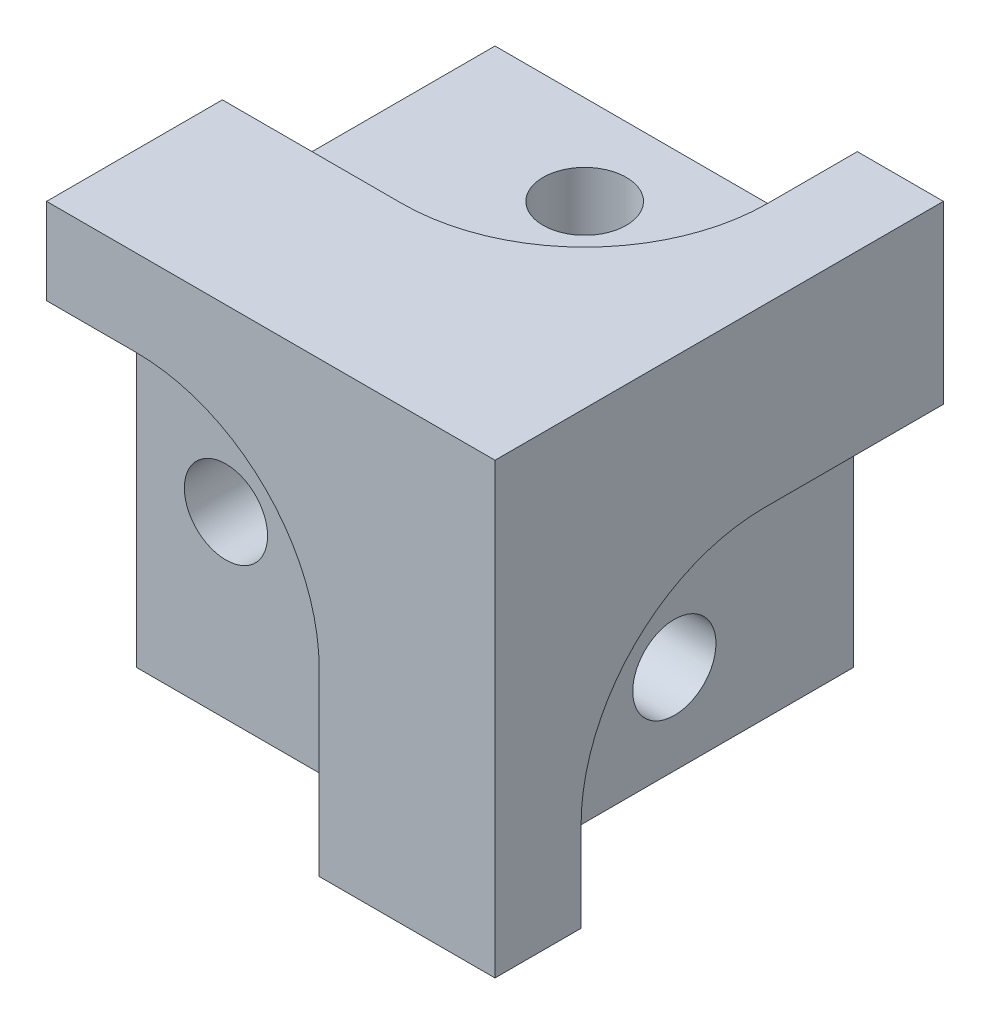
SolidWorks part; units mm, degrees
material "6061-T6 (SS)"
ref_plane "Front Plane" through (0, 0, 0) normal (0, 0, 1) x (1, 0, 0)
ref_plane "Top Plane" through (0, 0, 0) normal (0, 1, 0) x (1, 0, 0)
ref_plane "Right Plane" through (0, 0, 0) normal (1, 0, 0) x (0, 0, -1)
ref_axis "Axis1" [suppressed] through (0, 6.6, 0) along (0, -1, 0)
ref_axis "Axis2" [suppressed] through (0, 0, -6.6) along (0, 0, 1)
ref_plane "MIR-PLANE-1" through (0, 0, 0) normal (0, 0.7071, -0.7071) x (-1, 0, 0)
ref_plane "MIR-PLANE-2" through (0, 0, 0) normal (-0.7071, 0, 0.7071) x (0.7071, 0, 0.7071)
sketch "Sketch2" plane through (0, 0, 0) normal (0, 0, 1) x (1, 0, 0)
  line L1 (-7.9375, -7.9375) -> (7.9375, -7.9375)
  line L2 (-7.9375, -7.9375) -> (-7.9375, 7.9375)
  line L3 (-7.9375, 7.9375) -> (7.9375, 7.9375)
  line L4 (7.9375, -7.9375) -> (7.9375, 7.9375)
  line L5 (-7.9375, -7.9375) -> (7.9375, 7.9375) construction
  line L6 (-7.9375, 7.9375) -> (7.9375, -7.9375) construction
  point P0 (0, 0)
  dimension "D1" = 15.875
  dimension "D2" = 15.875
extrude "CUBE-BASE" add sketch "Sketch2" along normal blind 7.9375 and the other way blind 7.9375
hole_wizard "#4 Clearance Hole1" positions "Sketch3" profile "Sketch4" hole size "#4" standard "ANSI Inch" end condition through all
sketch "Sketch3" plane through (0, 0, 7.9375) normal (0, 0, 1) x (1, 0, 0)
  line L3 (7.9375, 7.9375) -> (-7.9375, 7.9375) construction
  line L4 (7.9375, -7.9375) -> (7.9375, 7.9375) construction
  point P6 (-4.7625, -1.5875)
  dimension "D1" = 12.7
  dimension "D2" = 9.525
sketch "Sketch4" plane through (-4.7625, -1.5875, 7.9375) normal (1, 0, 0) x (0, -1, 0)
  line L0 (0, 0) -> (0, 15.875)
  line L1 (0, 15.875) -> (1.4732, 15.875)
  line L2 (1.4732, 15.875) -> (1.4732, 0)
  line L5 (1.4732, 0) -> (0, 0)
  line L11 (0, -6.35) -> (0, 107.95) construction
  dimension "Thru Hole Dia." = 2.9464
  dimension "Thru Hole Depth" = 15.875
sketch "Sketch5" plane through (0, 0, 7.9375) normal (0, 0, 1) x (1, 0, 0)
  line L0 (-4.7625, 4.8895) -> (-7.9375, 4.8895)
  line L1 (-7.9375, -7.9375) -> (7.9375, -7.9375) construction
  line L2 (1.7145, -1.5875) -> (1.7145, -7.9375)
  line L4 (-7.9375, 7.9375) -> (-7.9375, -7.9375) construction
  line L5 (-7.9375, -7.9375) -> (1.7145, -7.9375)
  line L6 (-7.9375, 4.8895) -> (-7.9375, -7.9375)
  arc A0 (-4.7625, 4.8895) -> (1.7145, -1.5875) centre (-4.7625, -1.5875) cw
  circle A1 centre (-4.7625, -1.5875) radius 1.4732 construction
  circle A2 centre (-4.7625, -1.5875) radius 1.4732 construction
  point P11 (0, 0)
  dimension "D1" = 6.477
extrude "FRAME-RELIEF" cut sketch "Sketch5" against normal blind 3.175
mirror "Mirror1" [suppressed] about plane through (0, 0, 0) normal (0, 0.7071, -0.7071)
mirror "Mirror2" [suppressed] about plane through (0, 0, 0) normal (-0.7071, 0, 0.7071)
ref_axis "Axis3" through (7.9375, 7.9375, 7.9375) along (-0.5774, -0.5774, -0.5774)
pattern_circular "CirPattern1" count 3 over 360 about axis through (7.9375, 7.9375, 7.9375) along (-0.5774, -0.5774, -0.5774) of "FRAME-RELIEF", "#4 Clearance Hole1"
equation "\"D2@Sketch2\"=\"D1@Sketch2\""
equation "\"D1@CUBE-BASE\" = \"D1@Sketch2\" / 2"
equation "\"D2@CUBE-BASE\"=\"D1@Sketch2\"/2"
